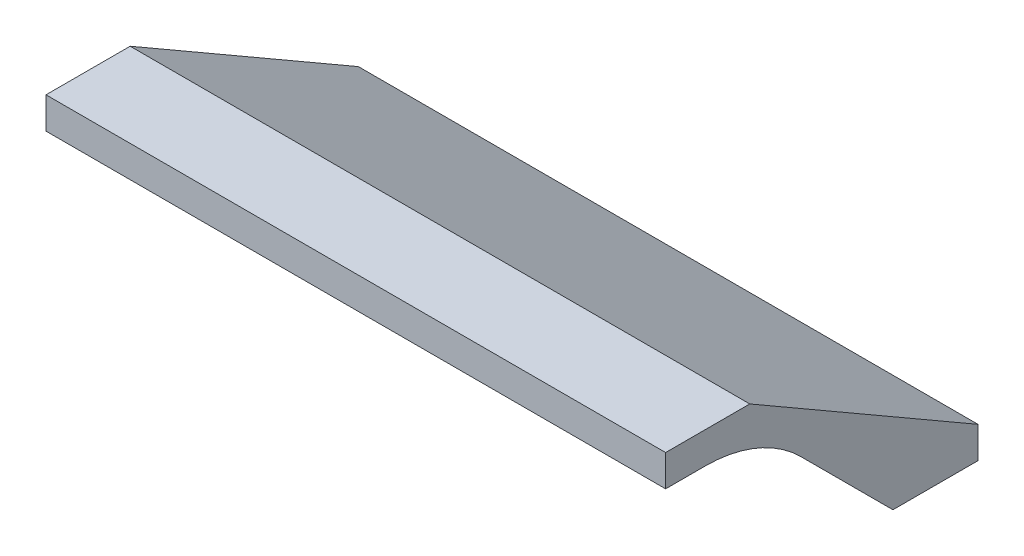
SolidWorks part; units mm, degrees
ref_plane "Front Plane" through (0, 0, 0) normal (0, 0, 1) x (1, 0, 0)
ref_plane "Top Plane" through (0, 0, 0) normal (0, 1, 0) x (1, 0, 0)
ref_plane "Right Plane" through (0, 0, 0) normal (1, 0, 0) x (0, 0, -1)
ref_plane "Plane1" through (-250, 0, 0) normal (-1, 0, 0) x (0, -1, 0)
sketch "Sketch1" plane through (-250, 0, 0) normal (-1, 0, 0) x (0, -1, 0)
  line L0 (106.3303, -252.0811) -> (106.3303, 0)
  line L1 (106.3303, 0) -> (-25.4013, 0)
  line L2 (-25.4013, 0) -> (-25.4013, -67.9095)
  line L3 (-25.4013, -67.9095) -> (80.9303, -252.0811)
  line L4 (80.9303, -252.0811) -> (106.3303, -252.0811)
extrude "Boss-Extrude1" add sketch "Sketch1" against normal blind 500
sketch "Sketch2" plane through (250, 0, 0) normal (1, 0, 0) x (0, 0, -1)
  line L0 (183.4273, -106.3303) -> (77.0971, 0)
  line L1 (77.0971, 0) -> (0, 0)
  line L2 (0, 0) -> (0, -106.3303)
  line L3 (0, -106.3303) -> (183.4273, -106.3303)
extrude "Cut-Extrude1" cut sketch "Sketch2" against normal through all
sketch "Sketch3" plane through (0, 0, 0) normal (0, -1, 0) x (1, 0, 0)
  line L0 (-50.8, -31.8107) -> (-139.7, -31.8107)
  line L1 (-139.7, -31.8107) -> (-139.7, -6.4107)
  line L2 (-139.7, -6.4107) -> (-50.8, -6.4107)
  line L3 (-50.8, -6.4107) -> (-50.8, -31.8107)
extrude "Boss-Extrude2" add sketch "Sketch3" along normal blind 1
sketch "Sketch4" plane through (0, 0, 0) normal (0, -1, 0) x (1, 0, 0)
  line L0 (50.8, -31.8107) -> (50.8, -6.4107)
  line L1 (50.8, -6.4107) -> (139.7, -6.4107)
  line L2 (139.7, -6.4107) -> (139.7, -31.8107)
  line L3 (139.7, -31.8107) -> (50.8, -31.8107)
extrude "Boss-Extrude3" add sketch "Sketch4" along normal blind 1
fillet "Fillet1" radius 109.331 1 edges at (0, 0, -77.0971) tangent propagation no
